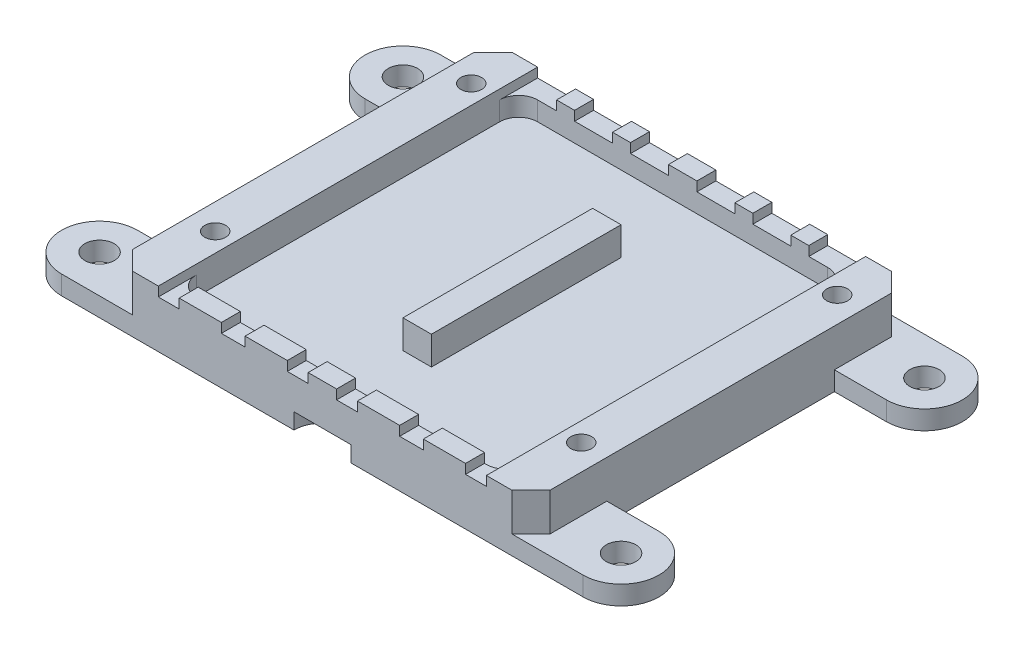
SolidWorks part; units mm, degrees
ref_plane "前视基准面" through (0, 0, 0) normal (0, 0, 1) x (1, 0, 0)
ref_plane "上视基准面" through (0, 0, 0) normal (0, 1, 0) x (1, 0, 0)
ref_plane "右视基准面" through (0, 0, 0) normal (1, 0, 0) x (0, 0, -1)
sketch "草图1" plane through (0, 0, 0) normal (0, 1, 0) x (1, 0, 0)
  line L0 (27.5, -20) -> (22, -20)
  line L2 (-22, -20) -> (-16, -20)
  line L3 (-16, 20) -> (16, 20)
  line L4 (-27.5, -12) -> (-22, -12)
  line L5 (-16, -20) -> (16, -20)
  line L6 (-22, 12) -> (-22, -12)
  line L7 (-22, 20) -> (22, -20) construction
  line L8 (-22, -20) -> (22, 20) construction
  line L9 (-22, 20) -> (-16, 20)
  line L10 (16, 20) -> (22, 20)
  line L11 (16, -20) -> (22, -20)
  line L12 (-27.5, 0) -> (-27.5, -16) construction
  line L13 (-27.5, -16) -> (27.5, -16) construction
  line L14 (27.5, -16) -> (27.5, 16) construction
  line L15 (27.5, 16) -> (-27.5, 16) construction
  line L16 (-27.5, 16) -> (-27.5, 0) construction
  line L17 (-22, -20) -> (-27.5, -20)
  line L18 (27.5, -12) -> (22, -12)
  line L19 (27.5, 12) -> (22, 12)
  line L20 (22, 20) -> (27.5, 20)
  line L21 (-22, 20) -> (-27.5, 20)
  line L22 (-27.5, 12) -> (-22, 12)
  line L23 (22, 12) -> (22, -12)
  circle A0 centre (-27.5, -16) radius 1.55
  circle A1 centre (-27.5, 16) radius 1.55
  circle A2 centre (27.5, 16) radius 1.55
  circle A3 centre (27.5, -16) radius 1.55
  arc A4 (27.5, -20) -> (27.5, -12) centre (27.5, -16) ccw
  arc A5 (-27.5, -12) -> (-27.5, -20) centre (-27.5, -16) ccw
  arc A6 (-27.5, 20) -> (-27.5, 12) centre (-27.5, 16) ccw
  arc A7 (27.5, 12) -> (27.5, 20) centre (27.5, 16) ccw
  point P5 (0, 0)
  point P31 (-22, 0)
  dimension "D1" = 40
  dimension "D2" = 44
extrude "凸台-拉伸1" add sketch "草图1" along normal blind 2
sketch "草图2" plane through (0, 2, 0) normal (0, 1, 0) x (1, 0, 0)
  line L0 (22, -20) -> (22, 20) construction
  line L1 (-27.5, -20) -> (27.5, -20) construction
  line L2 (-22, 20) -> (-22, -20) construction
  line L3 (27.5, 20) -> (-27.5, 20) construction
  line L4 (22, -20) -> (22, 20)
  line L5 (-22, -20) -> (22, -20)
  line L6 (-22, 20) -> (-22, -20)
  line L7 (22, 20) -> (-22, 20)
extrude "凸台-拉伸2" add sketch "草图2" along normal blind 4
sketch "草图3" plane through (0, 6, 0) normal (0, 1, 0) x (1, 0, 0)
  line L0 (-27.5525, 0) -> (27.6913, 0) construction
  line L1 (0, 25.4358) -> (0, -26.8932) construction
  line L2 (-1.5, 10) -> (-1.5, -10)
  line L3 (1.5, 10) -> (1.5, -10)
  line L15 (17.3, 18) -> (17.3, -18)
  line L16 (-17.3, 18) -> (-17.3, -18)
  line L20 (-22, -18) -> (22, -18)
  line L21 (-17.3, -18) -> (17.3, -18)
  line L22 (-17.3, 25.4358) -> (-17.3, -26.8932) construction
  line L23 (22, 18) -> (-22, 18)
  line L24 (17.3, 18) -> (-17.3, 18)
  line L25 (17.3, 25.4358) -> (17.3, -26.8932) construction
  line L26 (-1.5, -10) -> (1.5, -10)
  line L27 (-1.5, 10) -> (1.5, 10)
  line L28 (-27.5525, 10) -> (27.6913, 10) construction
  line L29 (-1.5, 25.4358) -> (-1.5, -26.8932) construction
  line L30 (-27.5525, -10) -> (27.6913, -10) construction
  line L31 (1.5, 25.4358) -> (1.5, -26.8932) construction
  dimension "D5" = 2
  dimension "D1" = 1.5
  dimension "D2" = 1.5
  dimension "D3" = 15.8
  dimension "D4" = 15.8
  dimension "D6" = 2
  dimension "D7" = 10
  dimension "D8" = 10
extrude "切除-拉伸1" cut sketch "草图3" against normal blind 3
sketch "草图4" plane through (0, 6, 0) normal (0, 1, 0) x (1, 0, 0)
  line L0 (-27.4831, 0) -> (27.2055, 0) construction
  line L1 (0, 25.5746) -> (0, -24.6723) construction
  line L2 (17.3, -18) -> (17.3, 18) construction
  line L3 (-17.3, 18) -> (-17.3, -18) construction
  line L4 (17.3, -20) -> (17.3, -18)
  line L5 (-17.3, 20) -> (-17.3, 18)
  line L6 (22, 20) -> (-22, 20) construction
  line L7 (-22, -20) -> (22, -20) construction
  line L8 (17.3, 20) -> (13.3, 20)
  line L9 (-17.3, -20) -> (-15.1, -20)
  line L10 (-13.3, 20) -> (-13.3, 18)
  line L11 (13.3, 18) -> (13.3, 20)
  line L12 (13.3, -18) -> (13.3, 20) construction
  line L13 (-13.3, 20) -> (-13.3, -18) construction
  line L14 (17.3, 18) -> (-17.3, 18) construction
  line L15 (17.3, 18) -> (13.3, 18)
  line L16 (-17.3, -18) -> (-17.3, -20)
  line L17 (-17.3, 20) -> (-17.3, -18) construction
  line L18 (17.3, 18) -> (17.3, 20)
  line L19 (17.3, -18) -> (17.3, 20) construction
  line L21 (-1.5, 10) -> (-1.5, -10) construction
  line L22 (1.5, -10) -> (1.5, 10) construction
  line L23 (-1.5, 20) -> (-1.5, 18)
  line L24 (5.5, 18) -> (5.5, 20)
  line L25 (-5.5, 20) -> (-5.5, 18)
  line L26 (1.5, -10) -> (1.5, 10) construction
  line L27 (-5.5, 20) -> (-5.5, -10) construction
  line L28 (-1.5, 20) -> (-5.5, 20)
  line L29 (-1.5, 18) -> (-5.5, 18)
  line L30 (1.5, 18) -> (1.5, 20)
  line L31 (-1.5, 10) -> (-1.5, -10) construction
  line L33 (-1.5, 20) -> (-1.5, -10) construction
  line L34 (1.5, -20) -> (3.7, -20)
  line L35 (1.5, -18) -> (3.7, -18)
  line L36 (-9.4, 25.5746) -> (-9.4, -24.6723) construction
  line L37 (9.4, 25.5746) -> (9.4, -24.6723) construction
  line L38 (7.4, 20) -> (7.4, 18)
  line L39 (11.4, 20) -> (11.4, 18)
  line L40 (-7.4, 20) -> (-7.4, 18)
  line L41 (-11.4, 20) -> (-11.4, 18)
  line L42 (-13.3, 20) -> (-17.3, 20)
  line L43 (-13.3, 18) -> (-17.3, 18)
  line L44 (-7.4, 20) -> (-11.4, 20)
  line L45 (-7.4, 18) -> (-11.4, 18)
  line L46 (5.5, 20) -> (1.5, 20)
  line L47 (5.5, 18) -> (1.5, 18)
  line L48 (11.4, 20) -> (7.4, 20)
  line L49 (11.4, 18) -> (7.4, 18)
  line L50 (-11.4, 25.5746) -> (-11.4, -24.6723) construction
  line L51 (-7.4, 25.5746) -> (-7.4, -24.6723) construction
  line L52 (7.4, 25.5746) -> (7.4, -24.6723) construction
  line L53 (11.4, 25.5746) -> (11.4, -24.6723) construction
  line L54 (-17.3, -18) -> (17.3, -18) construction
  line L55 (-17.3, -18) -> (-15.1, -18)
  line L56 (-15.1, -18) -> (-15.1, -20)
  line L57 (15.1, -20) -> (15.1, -18)
  line L58 (1.5, -18) -> (1.5, -20)
  line L59 (-1.5, -18) -> (-1.5, -20)
  line L60 (-3.7, -18) -> (-3.7, -20)
  line L61 (3.7, -18) -> (3.7, -20)
  line L62 (-10.65, -18) -> (-10.65, -20)
  line L63 (-8.15, -18) -> (-8.15, -20)
  line L64 (8.15, -18) -> (8.15, -20)
  line L65 (10.65, -18) -> (10.65, -20)
  line L66 (8.15, -18) -> (10.65, -18)
  line L67 (8.15, -20) -> (10.65, -20)
  line L68 (15.1, -18) -> (17.3, -18)
  line L69 (15.1, -20) -> (17.3, -20)
  line L70 (-3.7, -18) -> (-1.5, -18)
  line L71 (-3.7, -20) -> (-1.5, -20)
  line L72 (-10.65, -18) -> (-8.15, -18)
  line L73 (-10.65, -20) -> (-8.15, -20)
  line L74 (-10.65, 25.5746) -> (-10.65, -24.6723) construction
  line L75 (-8.15, 25.5746) -> (-8.15, -24.6723) construction
  line L76 (8.15, 25.5746) -> (8.15, -24.6723) construction
  line L77 (10.65, 25.5746) -> (10.65, -24.6723) construction
  dimension "D5" = 9.4
  dimension "D11" = 2.2
  dimension "D3" = 2
  dimension "D19" = 4
  dimension "D1" = 4
  dimension "D2" = 4
  dimension "D4" = 4
  dimension "D6" = 9.4
  dimension "D7" = 2
  dimension "D8" = 2
  dimension "D9" = 2
  dimension "D10" = 2
  dimension "D12" = 2.2
  dimension "D13" = 2.2
  dimension "D14" = 2.2
  dimension "D15" = 1.25
  dimension "D16" = 1.25
  dimension "D17" = 1.25
  dimension "D18" = 1.25
extrude "切除-拉伸2" cut sketch "草图4" against normal blind 1
fillet "圆角2" radius 2 4 edges at (17.3, 4, -18) (-17.3, 4, -18) (-17.3, 4, 18) (17.3, 4, 18)
sketch "草图5" plane through (0, 6, 0) normal (0, 1, 0) x (1, 0, 0)
  line L0 (-29.4032, 0) -> (28.1262, 0) construction
  line L1 (0, 28.1432) -> (0, -32.3448) construction
  line L8 (-22, 20) -> (-22, -20) construction
  line L9 (22, -20) -> (22, 20) construction
  circle A0 centre (19.3, 15) radius 1.1
  circle A1 centre (19.3, -12) radius 1.1
  circle A2 centre (-19.3, -12) radius 1.1
  circle A3 centre (-19.3, 15) radius 1.1
  dimension "D1" = 2.2
  dimension "D2" = 2.7
  dimension "D3" = 2.7
  dimension "D4" = 15
  dimension "D5" = 12
extrude "切除-拉伸3" cut sketch "草图5" against normal through all
sketch "草图6" plane through (0, 0, 0) normal (0, -1, 0) x (1, 0, 0)
  circle A0 centre (19.3, 12) radius 2
  circle A1 centre (-19.3, 12) radius 2
  circle A2 centre (-19.3, -15) radius 2
  circle A3 centre (19.3, -15) radius 2
  dimension "D1" = 4
extrude "切除-拉伸4" cut sketch "草图6" against normal blind 2.5
chamfer "Chamfer3" distance 2 angle 45 4 edges at (22, 4, 20) (-22, 4, 20) (-22, 4, -20) (22, 4, -20)
sketch "Sketch1" plane through (0, 0, 0) normal (0, -1, 0) x (1, 0, 0)
  line L0 (0, 0) -> (0, -20) construction
  line L1 (0, 0) -> (0, 20) construction
  line L2 (-27.5, 20) -> (27.5, 20) construction
  circle A0 centre (0, -20) radius 3
  circle A1 centre (0, 20) radius 3
extrude "Cut-Extrude1" cut sketch "Sketch1" against normal blind 1.67
